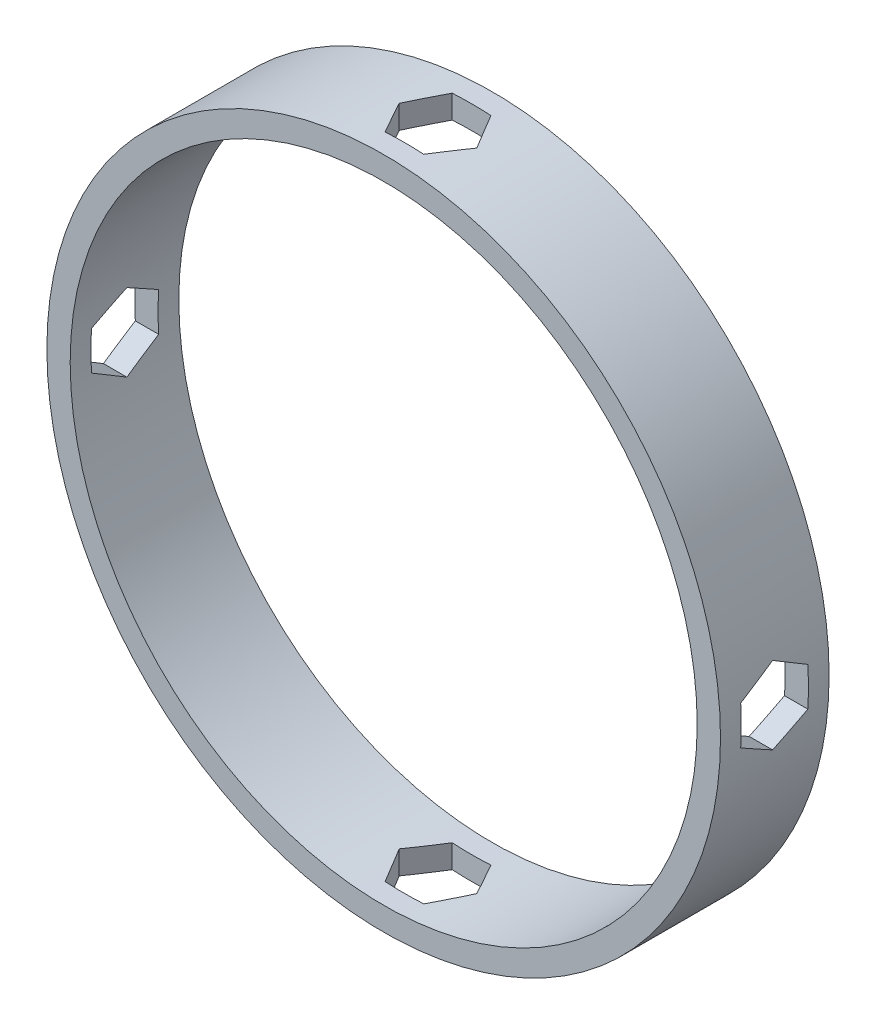
SolidWorks part; units mm, degrees
ref_plane "Front Plane" through (0, 0, 0) normal (0, 0, 1) x (1, 0, 0)
ref_plane "Top Plane" through (0, 0, 0) normal (0, 1, 0) x (1, 0, 0)
ref_plane "Right Plane" through (0, 0, 0) normal (1, 0, 0) x (0, 0, -1)
sketch "Sketch1" plane through (0, 0, 0) normal (0, 0, 1) x (1, 0, 0)
  circle A0 centre (0, 0) radius 34.11
  circle A1 centre (0, 0) radius 31.75
  dimension "D1" = 68.22
  dimension "D2" = 63.5
extrude "Boss-Extrude1" add sketch "Sketch1" along normal blind 10.5 and the other way blind 0.5
ref_plane "Plane1" through (0, 34.11, 0) normal (0, 1, 0) x (1, 0, 0)
sketch "Sketch2" plane through (0, 34.11, 0) normal (0, 1, 0) x (1, 0, 0)
  line L0 (0, -5) -> (-3.926, -5) construction
  line L1 (3.926, -5) -> (1.963, -1.6)
  line L2 (1.963, -1.6) -> (-1.963, -1.6)
  line L3 (-1.963, -1.6) -> (-3.926, -5)
  line L4 (-3.926, -5) -> (-1.963, -8.4)
  line L5 (-1.963, -8.4) -> (1.963, -8.4)
  line L6 (1.963, -8.4) -> (3.926, -5)
  circle A1 centre (0, -5) radius 3.4 construction
  dimension "D2" = 5
  dimension "D3" = 6.8
extrude "Cut-Extrude1" cut sketch "Sketch2" against normal through all
pattern_circular "CirPattern2" count 2 every 90 about axis through (0, 0, 10.5) along (0, 0, 1) of "Cut-Extrude1"
